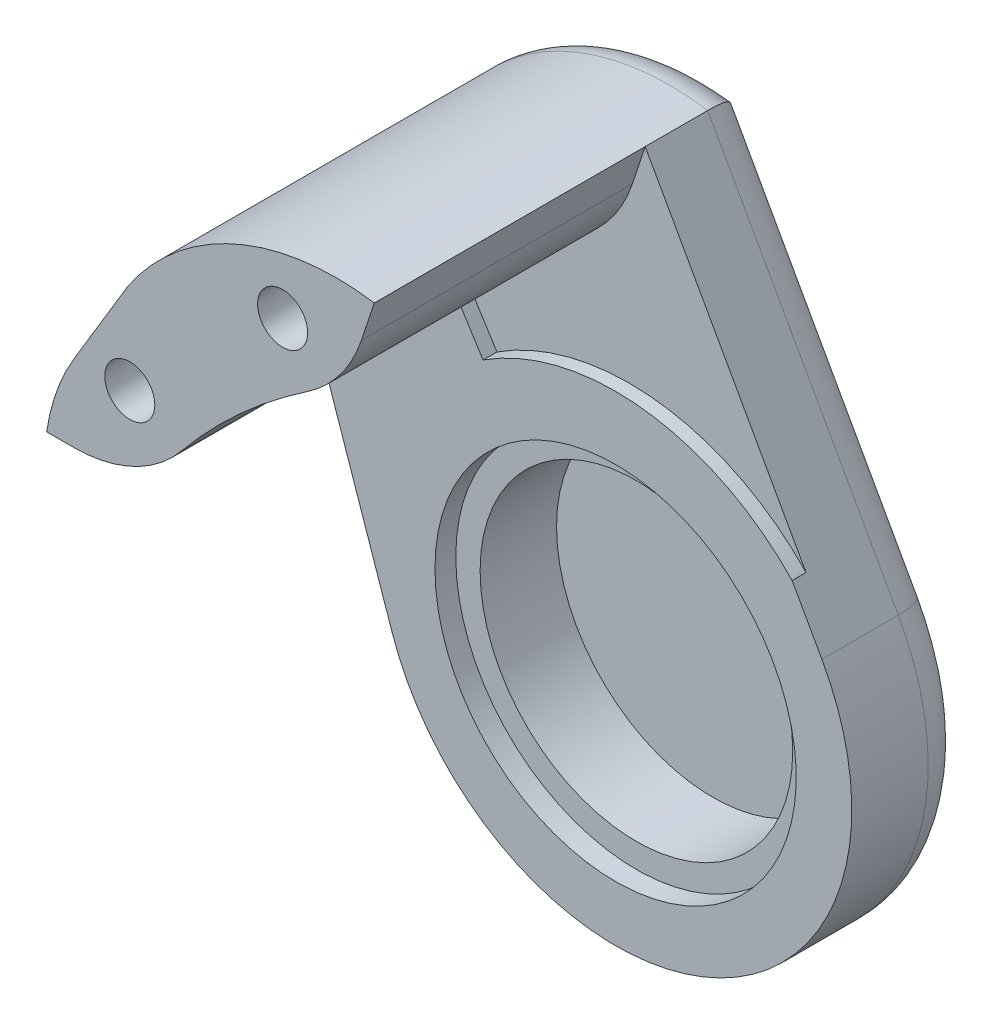
SolidWorks part; units mm, degrees
material "ABS"
ref_plane "Front Plane" through (0, 0, 0) normal (0, 0, 1) x (1, 0, 0)
ref_plane "Top Plane" through (0, 0, 0) normal (0, 1, 0) x (1, 0, 0)
ref_plane "Right Plane" through (0, 0, 0) normal (1, 0, 0) x (0, 0, -1)
sketch "Sketch1" plane through (0, 0, 0) normal (0, 0, 1) x (1, 0, 0)
  line L0 (-21.5118, -23.5649) -> (-14.5118, -23.5649)
  line L1 (0, -9.9671) -> (2.0631, -3.7458)
  line L3 (-15.6677, -11.5659) -> (-19.5301, -18.0027)
  arc A1 (-19.5301, -18.0027) -> (-21.5118, -23.5649) centre (-6.6677, -25.7195) ccw
  arc A2 (-15.6677, -11.5659) -> (2.0631, -3.7458) centre (-0.6677, -21.5651) cw
  arc A3 (-14.5118, -23.5649) -> (0, -9.9671) centre (21.0043, -46.9259) cw
  circle A4 centre (-4.5301, -8.0036) radius 1.8
  circle A5 centre (-15.5301, -18.0027) radius 1.8
  dimension "D1" = 7
  dimension "D8" = 3.6
  dimension "D2" = 2.0631
  dimension "D3" = 3.7458
  dimension "D4" = 16.9817
  dimension "D5" = 15.5614
  dimension "D6" = 5.9817
  dimension "D7" = 5.5622
extrude "Boss-Extrude1" add sketch "Sketch1" along normal blind 23
sketch "Sketch2" plane through (0, 0, 23) normal (0, 0, 1) x (1, 0, 0)
  line L0 (-15.6677, -11.5659) -> (-19.5301, -18.0027) construction
  line L1 (-15.6677, -11.5659) -> (-19.5301, -18.0027)
  line L2 (2.0631, -3.7458) -> (15.7796, -28.3476)
  line L3 (-21.5118, -23.5649) -> (-15.1513, -42.1348)
  arc A0 (-19.5301, -18.0027) -> (-21.5118, -23.5649) centre (-6.6677, -25.7195) ccw construction
  arc A1 (2.0631, -3.7458) -> (-15.6677, -11.5659) centre (-0.6677, -21.5651) ccw construction
  arc A2 (-19.5301, -18.0027) -> (-21.5118, -23.5649) centre (-6.6677, -25.7195) ccw
  arc A3 (2.0631, -3.7458) -> (-15.6677, -11.5659) centre (-0.6677, -21.5651) ccw
  arc A4 (15.7796, -28.3476) -> (-15.1513, -42.1348) centre (0.9315, -36.6261) cw
  circle A5 centre (-15.5301, -18.0027) radius 1.8 construction
  circle A6 centre (-4.5301, -8.0036) radius 1.8 construction
  circle A7 centre (-15.5301, -18.0027) radius 1.8
  circle A8 centre (-4.5301, -8.0036) radius 1.8
  dimension "D1" = 17
  dimension "D2" = 22.4433
  dimension "D3" = 13.0611
extrude "Boss-Extrude2" add sketch "Sketch2" along normal blind 4 and the other way blind 4.5
sketch "Sketch3" plane through (0, 0, 18.5) normal (0, 0, -1) x (-1, 0, 0)
  circle A0 centre (-0.9315, -36.6261) radius 11.25
  dimension "D1" = 22.5
  dimension "D2" = 32.8803
  dimension "D3" = 22.4433
extrude "Cut-Extrude1" cut sketch "Sketch3" against normal blind 7
sketch "Sketch4" plane through (0, 0, 18.5) normal (0, 0, -1) x (-1, 0, 0)
  circle A0 centre (-0.9315, -36.6261) radius 13
  dimension "D1" = 26
extrude "Cut-Extrude2" cut sketch "Sketch4" against normal blind 1.5
sketch "Sketch5" plane through (0, 0, 27) normal (0, 0, 1) x (1, 0, 0)
  circle A0 centre (-4.5301, -8.0036) radius 3
  circle A1 centre (-15.5301, -18.0027) radius 3
  dimension "D1" = 6
extrude "Cut-Extrude3" cut sketch "Sketch5" against normal blind 12
fillet "Fillet1" radius 3 6 edges at (-20.7974, -20.6853, 27) (8.9213, -16.0467, 27) (7.8526, -52.1534, 27) (-17.5989, -14.7843, 27) (-7.9425, -5.0708, 27) (-18.3315, -32.8499, 27)
sketch "Sketch6" plane through (0, 0, 18.5) normal (0, 0, -1) x (-1, 0, 0)
  line L0 (-2.0631, -3.7458) -> (0, -9.9671)
  line L1 (-2.0631, -3.7458) -> (-13.6368, -24.5042)
  line L2 (-15.7796, -28.3476) -> (-2.0631, -3.7458) construction
  line L3 (10.6831, -18.5879) -> (8.6095, -21.8839)
  arc A0 (-13.6368, -24.5042) -> (8.6095, -21.8839) centre (-0.9315, -36.6261) cw
  arc A1 (0, -9.9671) -> (10.6831, -18.5879) centre (-21.0043, -46.9259) cw
  arc A2 (14.5118, -23.5649) -> (0, -9.9671) centre (-21.0043, -46.9259) ccw construction
  dimension "D1" = 42.5104
  dimension "D2" = 17.5603
  dimension "D3" = 3.2959
  dimension "D4" = 10.6831
  dimension "D5" = 2.0736
  dimension "D6" = 11.5737
extrude "Cut-Extrude4" cut sketch "Sketch6" against normal blind 1
fillet "Fillet2" radius 10 2 edges at (-14.5118, -23.5649, 9.25) (0, -9.9671, 9.75)
ref_plane "Plane1" through (0, 0, -10) normal (0, 0, 1) x (1, 0, 0)
mirror "Mirror2" about plane through (0, 0, -10) normal (0, 0, 1) of bodies 106
sketch "Sketch8" plane through (-0.0194, -0.0108, 0) normal (0.8734, 0.487, 0) x (0, 0, -1)
  line L1 (-56.4869, 49.716) -> (3.681, 49.716)
  line L2 (-56.4869, 49.716) -> (-56.4869, -52.6244)
  line L3 (-56.4869, -52.6244) -> (3.681, -52.6244)
  line L4 (3.681, 49.716) -> (3.681, -52.6244)
  line L5 (-56.4869, 49.716) -> (3.681, -52.6244) construction
  line L6 (-56.4869, -52.6244) -> (3.681, 49.716) construction
  point P0 (-26.403, -1.4542)
extrude "Cut-Extrude5" cut sketch "Sketch8" against normal through all both and the other way through all
